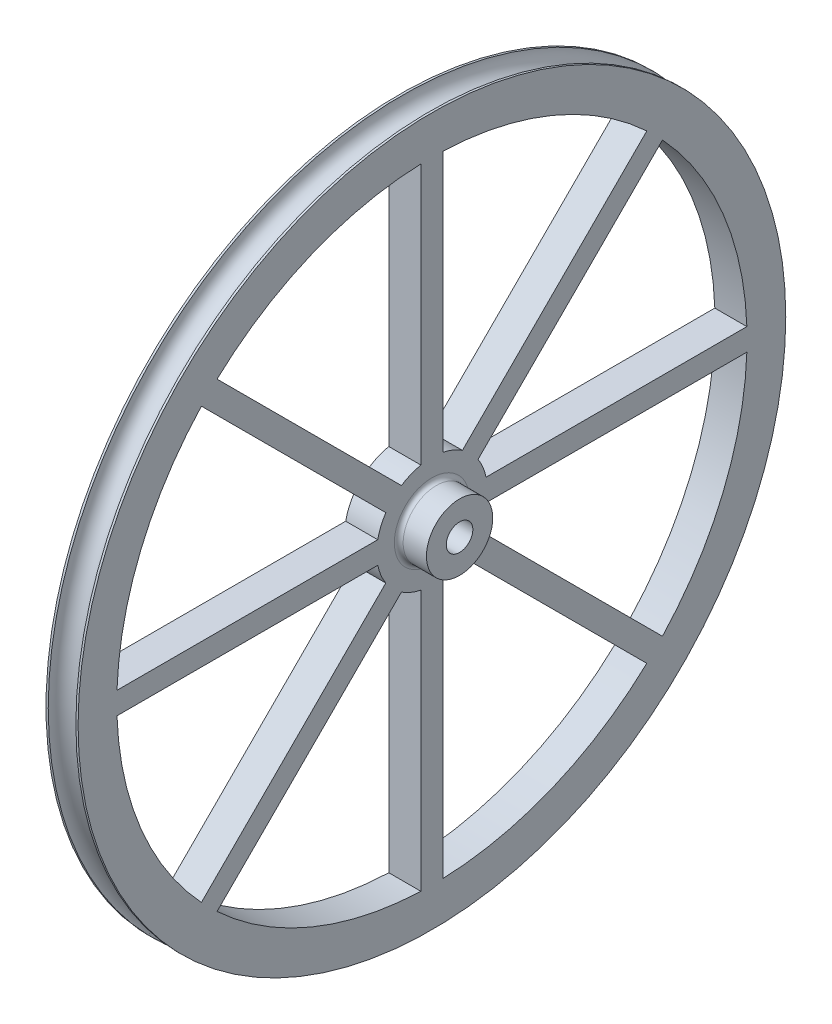
SolidWorks part; units mm, degrees
ref_plane "Front Plane" through (0, 0, 0) normal (0, 0, 1) x (1, 0, 0)
ref_plane "Top Plane" through (0, 0, 0) normal (0, 1, 0) x (1, 0, 0)
ref_plane "Right Plane" through (0, 0, 0) normal (1, 0, 0) x (0, 0, -1)
sketch "Sketch1" plane through (0, 0, 0) normal (1, 0, 0) x (0, 0, -1)
  circle A0 centre (0, 0) radius 40.64
  dimension "D1" = 81.28
extrude "Boss-Extrude1" add sketch "Sketch1" along normal blind 3.683
sketch "Sketch10" plane through (0, 0, 0) normal (0, 0, 1) x (1, 0, 0)
  line L0 (3.683, 40.64) -> (0, 40.64) construction
  line L1 (-1.0162, 0) -> (5.466, 0) construction
  line L2 (55, 0) -> (-55, 0) construction
  circle A0 centre (1.8415, 40.64) radius 1.5875
  dimension "D1" = 3.175
revolve "Cut-Revolve1" cut sketch "Sketch10" angle 360 about L1
sketch "Sketch11" plane through (3.683, 0, 0) normal (1, 0, 0) x (0, 0, -1)
  line L2 (0, -50.6508) -> (0, 43.6326) construction
  line L3 (-53.144, 0) -> (6.35, 0) construction
  line L4 (-1.27, 36.1727) -> (-1.27, 6.2217)
  line L5 (1.27, 36.1727) -> (1.27, 6.2217)
  line L6 (24.6799, 26.476) -> (3.5014, 5.2974)
  line L7 (26.476, 24.6799) -> (5.2974, 3.5014)
  line L8 (36.1727, 1.27) -> (6.2217, 1.27)
  line L9 (36.1727, -1.27) -> (6.2217, -1.27)
  line L10 (26.476, -24.6799) -> (5.2974, -3.5014)
  line L11 (24.6799, -26.476) -> (3.5014, -5.2974)
  line L12 (1.27, -36.1727) -> (1.27, -6.2217)
  line L13 (-1.27, -36.1727) -> (-1.27, -6.2217)
  line L14 (-24.6799, -26.476) -> (-3.5014, -5.2974)
  line L15 (-26.476, -24.6799) -> (-5.2974, -3.5014)
  line L16 (-36.1727, -1.27) -> (-6.2217, -1.27)
  line L17 (-36.1727, 1.27) -> (-6.2217, 1.27)
  line L18 (-26.476, 24.6799) -> (-5.2974, 3.5014)
  line L19 (-24.6799, 26.476) -> (-3.5014, 5.2974)
  arc A2 (5.2974, -3.5014) -> (6.2217, -1.27) centre (0, 0) ccw
  arc A3 (-26.476, 24.6799) -> (-36.1727, 1.27) centre (0, 0) ccw
  arc A4 (24.6799, 26.476) -> (1.27, 36.1727) centre (0, 0) ccw
  arc A5 (-1.27, 36.1727) -> (-24.6799, 26.476) centre (0, 0) ccw
  arc A6 (36.1727, 1.27) -> (26.476, 24.6799) centre (0, 0) ccw
  arc A7 (26.476, -24.6799) -> (36.1727, -1.27) centre (0, 0) ccw
  arc A8 (1.27, -36.1727) -> (24.6799, -26.476) centre (0, 0) ccw
  arc A9 (-24.6799, -26.476) -> (-1.27, -36.1727) centre (0, 0) ccw
  arc A10 (-36.1727, -1.27) -> (-26.476, -24.6799) centre (0, 0) ccw
  arc A11 (1.27, -6.2217) -> (3.5014, -5.2974) centre (0, 0) ccw
  arc A12 (-3.5014, -5.2974) -> (-1.27, -6.2217) centre (0, 0) ccw
  arc A13 (-6.2217, -1.27) -> (-5.2974, -3.5014) centre (0, 0) ccw
  arc A14 (-5.2974, 3.5014) -> (-6.2217, 1.27) centre (0, 0) ccw
  arc A15 (-1.27, 6.2217) -> (-3.5014, 5.2974) centre (0, 0) ccw
  arc A16 (3.5014, 5.2974) -> (1.27, 6.2217) centre (0, 0) ccw
  arc A17 (6.2217, 1.27) -> (5.2974, 3.5014) centre (0, 0) ccw
  point P43 (0, 0)
  dimension "D1" = 12.7
  dimension "D2" = 72.39
  dimension "D3" = 2.54
  dimension "D4" = 1.27
  dimension "D5" = 8
extrude "Cut-Extrude3" cut sketch "Sketch11" against normal through all
sketch "Sketch12" plane through (3.683, 0, 0) normal (1, 0, 0) x (0, 0, -1)
  circle A0 centre (0, 0) radius 1.524
  dimension "D1" = 3.048
extrude "Cut-Extrude4" cut sketch "Sketch12" against normal through all
sketch "Sketch13" plane through (3.683, 0, 0) normal (1, 0, 0) x (0, 0, -1)
  circle A0 centre (0, 0) radius 3.81
  circle A1 centre (0, 0) radius 1.524
  circle A2 centre (0, 0) radius 1.524 construction
  dimension "D1" = 7.62
extrude "Boss-Extrude2" add sketch "Sketch13" along normal blind 3.175
fillet "Fillet1" radius 0.508 1 edges at (3.683, 0, -3.81)
